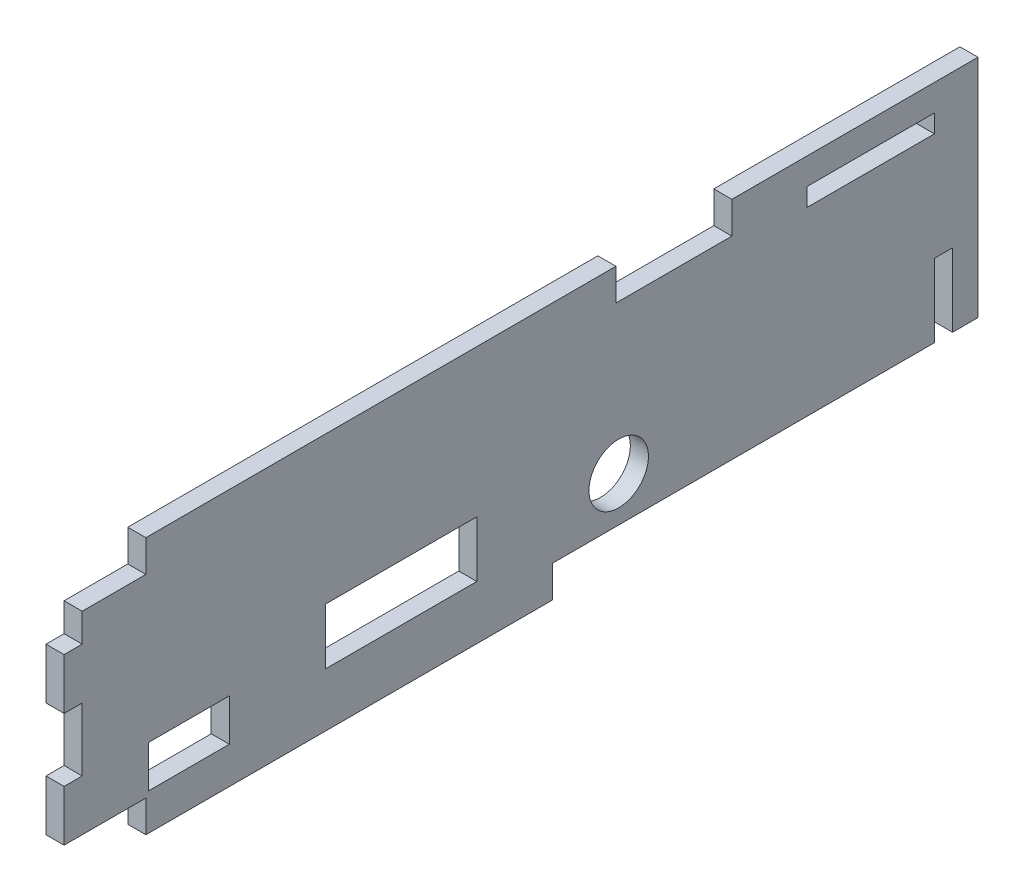
SolidWorks part; units mm, degrees
ref_plane "Front" through (0, 0, 0) normal (0, 0, 1) x (1, 0, 0)
ref_plane "Top" through (0, 0, 0) normal (0, 1, 0) x (1, 0, 0)
ref_plane "Right" through (0, 0, 0) normal (1, 0, 0) x (0, 0, -1)
sketch "Sketch2" plane through (0, 0, 0) normal (1, 0, 0) x (0, 0, -1)
  line L0 (0, 4.7244) -> (84.963, 4.7244) construction
  line L1 (0, 24.0284) -> (84.963, 24.0284)
  line L2 (0, 24.0284) -> (0, 0)
  line L3 (0, 0) -> (84.963, 0)
  line L4 (84.963, 24.0284) -> (84.963, 0)
  line L5 (6.6294, 9.3853) -> (14.6685, 9.3853)
  line L6 (6.6294, 9.3853) -> (6.6294, 5.207)
  line L7 (6.6294, 5.207) -> (14.6685, 5.207)
  line L8 (14.6685, 9.3853) -> (14.6685, 5.207)
  line L9 (24.257, 6.9215) -> (39.3446, 6.9215)
  line L10 (24.257, 6.9215) -> (24.257, 12.5095)
  line L11 (24.257, 12.5095) -> (39.3446, 12.5095)
  line L12 (39.3446, 6.9215) -> (39.3446, 12.5095)
  line L13 (53.486, 12.1412) -> (53.486, 4.7244) construction
  line L14 (6.35, 24.0284) -> (6.35, 27.2034)
  line L15 (6.35, 27.2034) -> (53.213, 27.2034)
  line L16 (84.963, 24.0284) -> (86.7664, 24.0284)
  line L17 (6.35, 4.7244) -> (6.35, 1.5494)
  line L18 (6.35, 1.5494) -> (46.863, 1.5494)
  line L19 (46.863, 1.5494) -> (46.863, 4.7244)
  line L20 (46.863, 4.7244) -> (84.963, 4.7244)
  line L21 (6.35, 4.7244) -> (0, 4.7244)
  line L22 (86.7664, 24.0284) -> (86.7664, 4.7244)
  line L23 (86.7664, 24.0284) -> (89.3064, 24.0284)
  line L24 (89.3064, 24.0284) -> (89.3064, 4.7244)
  line L25 (84.963, 12.0142) -> (86.7664, 12.0142)
  line L26 (86.7664, 4.7244) -> (89.3064, 4.7244)
  line L27 (84.963, 22.7584) -> (72.263, 22.7584)
  line L28 (42.4815, 24.0284) -> (42.4815, -8.3898) construction
  line L29 (-1.8034, 4.7244) -> (0, 4.7244)
  line L30 (-1.8034, 9.8044) -> (-1.8034, 4.7244)
  line L31 (-1.8034, 9.8044) -> (0, 9.8044)
  line L32 (-1.8034, 16.1036) -> (0, 16.1036)
  line L33 (-1.8034, 21.1836) -> (-1.8034, 16.1036)
  line L34 (0, 21.1836) -> (-1.8034, 21.1836)
  line L35 (53.213, 27.2034) -> (53.213, 24.0284)
  line L36 (72.263, 22.7584) -> (72.263, 24.5618)
  line L37 (72.263, 24.5618) -> (84.963, 24.5618)
  line L38 (84.963, 24.5618) -> (84.963, 24.0284)
  line L39 (89.3064, 24.0284) -> (89.3064, 27.2034)
  line L40 (89.3064, 27.2034) -> (64.77, 27.2034)
  line L41 (64.77, 27.2034) -> (64.77, 24.0284)
  circle A0 centre (53.486, 9.1758) radius 2.9655
  dimension "D11" = 5.9309
  dimension "D13" = 11.176
  dimension "D1" = 84.963
  dimension "D2" = 8.0391
  dimension "D3" = 15.0876
  dimension "D4" = 4.6609
  dimension "D5" = 4.1783
  dimension "D6" = 6.6294
  dimension "D7" = 7.7851
  dimension "D8" = 5.588
  dimension "D9" = 9.5885
  dimension "D10" = 4.7244
  dimension "D12" = 7.4168
  dimension "D14" = 19.304
  dimension "D15" = 6.35
  dimension "D16" = 3.175
  dimension "D17" = 3.175
  dimension "D18" = 38.1
  dimension "D19" = 1.8034
  dimension "D20" = 2.8448
  dimension "D21" = 5.08
  dimension "D22" = 5.08
  dimension "D23" = 31.75
  dimension "D24" = 1.8034
  dimension "D25" = 1.27
  dimension "D26" = 12.7
extrude "Boss-Extrude1" add sketch "Sketch2" along normal blind 1.8034 contours L21 L17 L18 L19 L20 L4 L1 L2 A0 L12 L9 L10 L11 L5 L8 L7 L6 | L23 L4 | L4 | L15 L14 L1 | L2 L34 L33 L32 | L31 L30 L29 L2 | L22 L26 L24 L23 | L40 L41 L1 L36 L37 L38 L16 L23 L39 region at (0, 13.8682, -41.8848) region at (0, 25.6159, -29.7815) region at (0, 18.6436, 0.9017) region at (0, 25.7417, -76.8882) region at (0, 7.2644, 0.9017) region at (0, 18.0213, -85.8647) region at (0, 14.3764, -88.0364)
